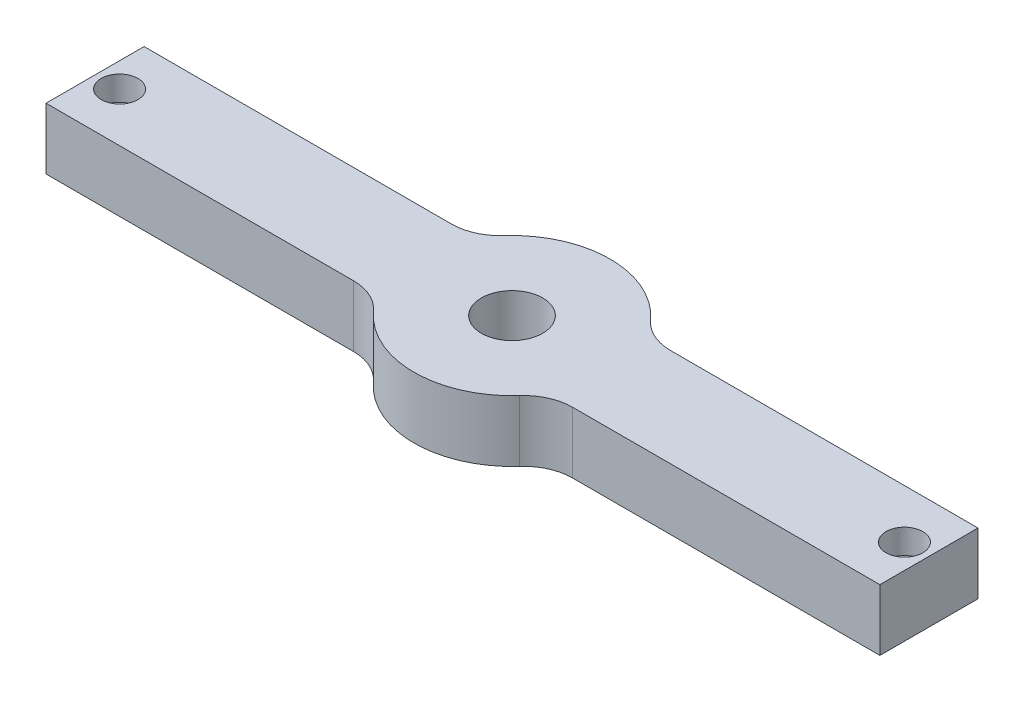
SolidWorks part; units mm, degrees
ref_plane "Front Plane" through (0, 0, 0) normal (0, 0, 1) x (1, 0, 0)
ref_plane "Top Plane" through (0, 0, 0) normal (0, 1, 0) x (1, 0, 0)
ref_plane "Right Plane" through (0, 0, 0) normal (1, 0, 0) x (0, 0, -1)
sketch "Sketch2" plane through (0, 0, 0) normal (0, 1, 0) x (1, 0, 0)
  line L0 (-21.997, 0) -> (0, 0) construction
  line L1 (-107.95, -25.4) -> (-21.997, -25.4)
  line L2 (-107.95, -25.4) -> (-107.95, 0)
  line L3 (-107.95, 0) -> (-21.997, 0)
  line L4 (-21.997, -25.4) -> (-21.997, 0)
  line L5 (21.997, -25.4) -> (107.95, -25.4)
  line L6 (21.997, -25.4) -> (21.997, 0)
  line L7 (21.997, 0) -> (107.95, 0)
  line L8 (107.95, -25.4) -> (107.95, 0)
  line L9 (0, 0) -> (21.997, 0) construction
  circle A0 centre (0, -12.7) radius 7.9375
  circle A1 centre (0, -12.7) radius 25.4
  point P13 (107.95, -12.7)
  dimension "D3" = 215.9
  dimension "D4" = 15.875
  dimension "D5" = 50.8
  dimension "D1" = 25.4
  dimension "D2" = 25.4
extrude "Boss-Extrude1" add sketch "Sketch2" along normal blind 15.875 contours A1 L3 L2 L1 | L4 A1 | L6 A1 L4 A0 | L6 A1 | A1 L5 L8 L7 region at (-66.1179, 0, 12.7) region at (-23.3664, 0, 12.7) region at (-21.325, 0, 12.7) region at (66.1179, 0, 12.7) region at (23.3664, 0, 12.7)
fillet "Fillet1" radius 12.7 4 edges at (21.997, 7.9375, 0) (21.997, 7.9375, 25.4) (-21.997, 7.9375, 25.4) (-21.997, 7.9375, 0)
sketch "Sketch3" plane through (0, 0, 0) normal (0, -1, 0) x (1, 0, 0)
  circle A0 centre (0, 12.7) radius 22.225
  dimension "D1" = 44.45
extrude "Cut-Extrude1" cut sketch "Sketch3" against normal blind 3.175
sketch "Sketch4" plane through (0, 15.875, 0) normal (0, 1, 0) x (1, 0, 0)
  line L0 (-107.95, -25.4) -> (-107.95, 0) construction
  line L1 (107.95, -25.4) -> (107.95, 0) construction
  circle A0 centre (-101.6, -12.7) radius 4.7625
  circle A1 centre (101.6, -12.7) radius 4.7625
  point P4 (-107.95, -12.7)
  point P5 (107.95, -12.7)
  point P8 (0, 0)
  point P11 (0, 0)
  point P12 (0, 0)
  point P13 (0, 0)
  point P14 (0, 0)
  point P15 (0, 0)
  point P16 (0, 0)
  point P17 (0, 0)
  point P18 (0, 0)
  point P19 (0, 0)
  point P20 (0, 0)
  point P21 (0, 0)
  point P22 (0, 0)
  point P23 (0, 0)
  dimension "D1" = 9.525
  dimension "D2" = 9.525
  dimension "D3" = 6.35
  dimension "D4" = 6.35
extrude "Cut-Extrude2" cut sketch "Sketch4" against normal blind 6.35
sketch "Sketch5" plane through (0, 9.525, 0) normal (0, 1, 0) x (1, 0, 0)
  circle A0 centre (-101.6, -12.7) radius 3.175
  circle A1 centre (101.6, -12.7) radius 3.175
  dimension "D1" = 6.35
  dimension "D2" = 6.35
extrude "Cut-Extrude3" cut sketch "Sketch5" against normal through all
